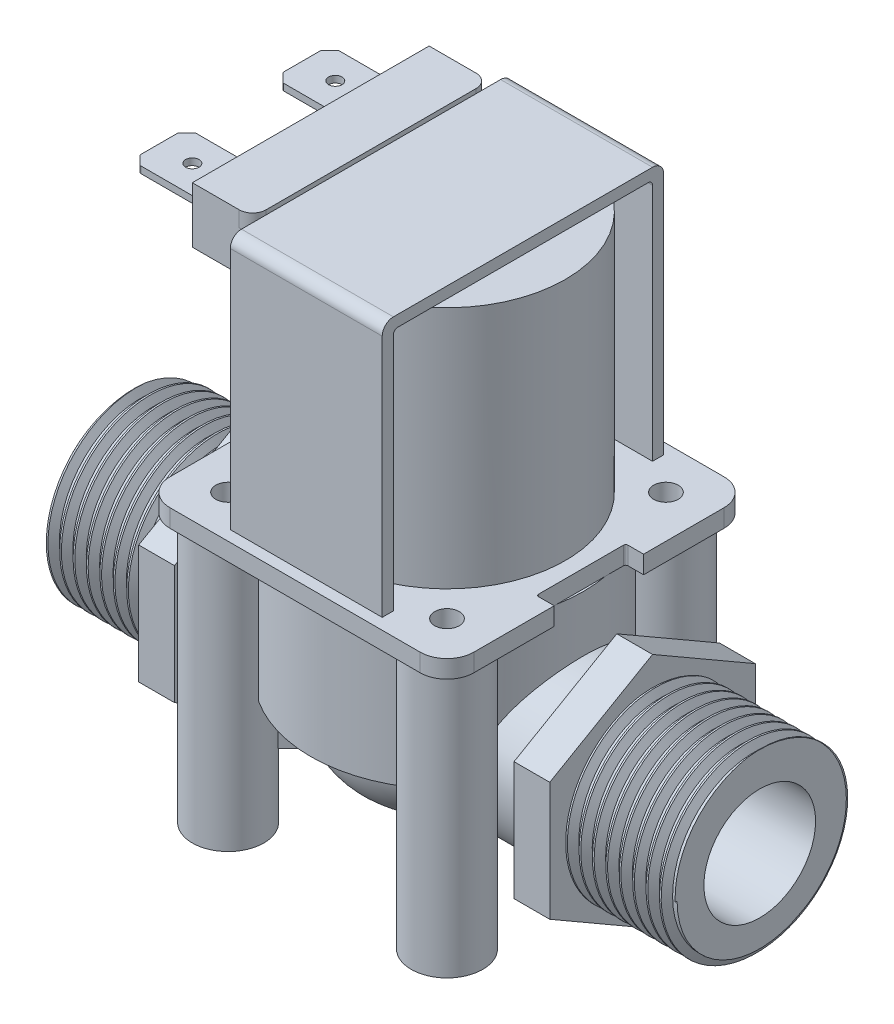
SolidWorks part; units mm, degrees
note: The reader was unsure of these and kept them because the rebuilt part matched: shared geometry of "Sketch14<3>".
ref_plane "Front Plane" through (0, 0, 0) normal (0, 0, 1) x (1, 0, 0)
ref_plane "Top Plane" through (0, 0, 0) normal (0, 1, 0) x (1, 0, 0)
ref_plane "Right Plane" through (0, 0, 0) normal (1, 0, 0) x (0, 0, -1)
sketch "Sketch1" plane through (0, 0, 0) normal (0, 1, 0) x (1, 0, 0)
  line L0 (-17, 17) -> (-13, 17)
  line L1 (-17, -17) -> (17, -17)
  line L2 (-17, -17) -> (-17, 17)
  line L3 (-17, 17) -> (17, 17)
  line L4 (17, -17) -> (17, 17)
  line L5 (-17, -17) -> (17, 17) construction
  line L6 (-17, 17) -> (17, -17) construction
  line L7 (0, 17) -> (0, -17)
  line L8 (17, -17) -> (12.25, -17)
  line L9 (12.25, -17) -> (12.25, -12.25)
  line L10 (-17, 0) -> (17, 0)
  circle A0 centre (12.25, -12.25) radius 1.375
  circle A1 centre (-12.25, -12.25) radius 1.375
  circle A2 centre (12.25, 12.25) radius 1.375
  circle A3 centre (-12.25, 12.25) radius 1.375
  point P0 (0, 0)
  dimension "D2" = 4.75
  dimension "D1" = 34
extrude "Boss-Extrude1" add sketch "Sketch1" along normal blind 2
fillet "Fillet1" radius 3 4 edges at (-17, 1, -17) (17, 1, -17) (17, 1, 17) (-17, 1, 17)
sketch "Sketch2" plane through (0, 2, 0) normal (0, 1, 0) x (1, 0, 0)
  line L0 (0, -17) -> (0, -15.125)
  line L1 (-14, -17) -> (14, -17) construction
  line L2 (-17, 0) -> (17, 0)
  line L3 (-8.5, -15.75) -> (8.5, -15.75)
  line L4 (-8.5, -15.75) -> (-8.5, -14.5)
  line L5 (-8.5, -14.5) -> (8.5, -14.5)
  line L6 (8.5, -15.75) -> (8.5, -14.5)
  line L7 (-8.5, -15.75) -> (8.5, -14.5) construction
  line L8 (-8.5, -14.5) -> (8.5, -15.75) construction
  line L9 (-17, -14) -> (-17, 14) construction
  line L10 (17, -14) -> (17, 14) construction
  line L11 (-8.5, 14.5) -> (8.5, 14.5)
  line L12 (8.5, 15.75) -> (8.5, 14.5)
  line L13 (-8.5, 15.75) -> (8.5, 15.75)
  line L14 (-8.5, 15.75) -> (-8.5, 14.5)
  dimension "D1" = 1.25
  dimension "D2" = 17
extrude "Boss-Extrude2" add sketch "Sketch2" along normal blind 28.5 contours L5 L6 L3 L4 | L11 L12 L13 L14
sketch "Sketch3" plane through (0, 30.5, 0) normal (0, 1, 0) x (1, 0, 0)
  line L1 (-8.5, 14.5) -> (8.5, 14.5)
  line L2 (-8.5, 14.5) -> (-8.5, -14.5)
  line L3 (-8.5, -14.5) -> (8.5, -14.5)
  line L4 (8.5, 14.5) -> (8.5, -14.5)
extrude "Boss-Extrude3" add sketch "Sketch3" against normal blind 1.25
fillet "Fillet2" radius 1.25 2 edges at (0, 30.5, -15.75) (0, 30.5, 15.75)
fillet "Fillet3" radius 0.5 2 edges at (0, 29.25, 14.5) (0, 29.25, -14.5)
sketch "Sketch4" plane through (0, 2, 0) normal (0, 1, 0) x (1, 0, 0)
  circle A0 centre (0, 0) radius 13.25
extrude "Boss-Extrude4" add sketch "Sketch4" along normal up to surface (27.25 mm away) up to face at (0, 29.25, 0)
sketch "Sketch5" plane through (0, 29.25, 0) normal (0, 1, 0) x (1, 0, 0)
  line L1 (0, 13.25) -> (-15.25, 13.25)
  line L2 (0, 13.25) -> (0, -13.25)
  line L3 (0, -13.25) -> (-15.25, -13.25)
  line L4 (-15.25, 13.25) -> (-15.25, -13.25)
  circle A0 centre (0, 0) radius 13.25 construction
  dimension "D1" = 15.25
extrude "Boss-Extrude5" add sketch "Sketch5" against normal blind 4.5 contours L2 L1 L4 L3
sketch "Sketch6" plane through (0, 29.25, 0) normal (0, 1, 0) x (1, 0, 0)
  line L1 (-15.25, 13.25) -> (-10, 13.25)
  line L2 (-15.25, 13.25) -> (-15.25, -13.25)
  line L3 (-15.25, -13.25) -> (-10, -13.25)
  line L4 (-8.5, 11.75) -> (-8.5, -11.75)
  arc A0 (-10, -13.25) -> (-8.5, -11.75) centre (-10, -11.75) ccw
  arc A1 (-8.5, 11.75) -> (-10, 13.25) centre (-10, 11.75) ccw
  point P8 (-8.5, -13.25)
  dimension "D1" = 1.5
extrude "Boss-Extrude6" add sketch "Sketch6" along normal offset from surface (1.75 mm away) 0.5 up to face at (0, 30.5, 0) offset beyond the face yes
sketch "Sketch7" plane through (-15.25, 0, 0) normal (-1, 0, 0) x (0, 0, 1)
  line L0 (13.25, 24.75) -> (13.25, 27.25)
  line L1 (-13.25, 24.75) -> (13.25, 24.75) construction
  line L2 (-13.25, 24.75) -> (13.25, 24.75) construction
  line L3 (13.25, 24.75) -> (13.25, 31) construction
  line L4 (13.25, 27.25) -> (12, 27.25)
  line L5 (12, 26.875) -> (12, 27.625)
  line L6 (0, 31) -> (0, 24.75)
  line L7 (12, 27.625) -> (4, 27.625)
  line L8 (12, 27.625) -> (12, 26.875)
  line L9 (12, 26.875) -> (4, 26.875)
  line L10 (4, 27.625) -> (4, 26.875)
  line L11 (13.25, 31) -> (-13.25, 31) construction
  line L12 (-12, 26.875) -> (-4, 26.875)
  line L13 (-4, 27.625) -> (-4, 26.875)
  line L14 (-12, 27.625) -> (-4, 27.625)
  line L15 (-12, 27.625) -> (-12, 26.875)
  point P12 (12, 27.25)
  dimension "D1" = 8
extrude "Boss-Extrude7" add sketch "Sketch7" along normal blind 9 contours L14 L15 L12 L13 | L7 L10 L9 L5
sketch "Sketch8" plane through (0, 27.625, 0) normal (0, 1, 0) x (1, 0, 0)
  line L0 (-24.25, 11.125) -> (-24.25, 4.875)
  line L1 (-24.25, 12) -> (-24.25, 4) construction
  line L2 (-15.25, 0) -> (-24.25, 0)
  line L7 (-15.25, -13.25) -> (-15.25, 13.25) construction
  line L12 (-16.25, -4) -> (-24.25, -4)
  line L13 (-24.25, 12) -> (-16.25, 12)
  line L14 (-24.25, 12) -> (-24.25, 11.125)
  line L15 (-24.25, 11.125) -> (-16.25, 11.125)
  line L16 (-16.25, 12) -> (-16.25, 11.125)
  line L17 (-16.25, 4.875) -> (-24.25, 4.875)
  line L18 (-16.25, 4.875) -> (-16.25, 4)
  line L19 (-16.25, 4) -> (-24.25, 4)
  line L20 (-24.25, 4.875) -> (-24.25, 4)
  line L21 (-24.25, -4.875) -> (-24.25, -4)
  line L22 (-16.25, -4.875) -> (-24.25, -4.875)
  line L23 (-16.25, -4.875) -> (-16.25, -4)
  line L24 (-24.25, -11.125) -> (-16.25, -11.125)
  line L25 (-16.25, -12) -> (-16.25, -11.125)
  line L26 (-24.25, -12) -> (-16.25, -12)
  line L27 (-24.25, -12) -> (-24.25, -11.125)
  point P5 (-24.25, 8)
  dimension "D1" = 8
extrude "Cut-Extrude1" cut sketch "Sketch8" against normal up to surface (0.75 mm away) contours L15 L16 L13 L14 | L20 L19 L18 L17 | L22 L21 L12 L23 | L24 L25 L26 L27 up to face at (-19.75, 26.875, 8)
chamfer "Chamfer1" distance 1 angle 45 4 edges at (-24.25, 27.25, 11.125) (-24.25, 27.25, 4.875) (-24.25, 27.25, -4.875) (-24.25, 27.25, -11.125)
fillet "Fillet4" radius 0.25 8 edges at (-23.25, 27.25, 11.125) (-24.25, 27.25, 10.125) (-24.25, 27.25, 5.875) (-23.25, 27.25, 4.875) (-24.25, 27.25, -10.125) (-23.25, 27.25, -11.125) (-24.25, 27.25, -5.875) (-23.25, 27.25, -4.875)
sketch "Sketch9" plane through (0, 0, 0) normal (0, -1, 0) x (1, 0, 0)
  line L0 (-17, 14) -> (-17, -14) construction
  line L1 (-17, -5) -> (-17, 5)
  line L2 (0, 17) -> (0, -17)
  line L3 (-17, 5) -> (-15, 5)
  line L4 (-17, 5) -> (-17, -5)
  line L5 (-17, -5) -> (-15, -5)
  line L6 (-15, 5) -> (-15, -5)
  line L7 (-14, 17) -> (14, 17) construction
  line L8 (-14, -17) -> (14, -17) construction
  line L9 (17, -5) -> (15, -5)
  line L10 (15, 5) -> (15, -5)
  line L11 (17, 5) -> (15, 5)
  line L12 (17, 5) -> (17, -5)
  point P5 (-17, 0)
  line M11 (-17, 14) -> (-17, -14)
  line M15 (17, -14) -> (17, 14)
  dimension "D1" = 2
extrude "Cut-Extrude2" cut sketch "Sketch9" against normal up to surface (2 mm away) contours L6 L3 L5 M11 | L11 L10 L9 M15 up to face at (0, 2, 13.25)
fillet "Fillet6" radius 0.25 4 edges at (15, 1, 5) (15, 1, -5) (-15, 1, 5) (-15, 1, -5)
sketch "Sketch10" plane through (0, 27.625, 0) normal (0, 1, 0) x (1, 0, 0)
  line L0 (-24.25, 8) -> (-21.25, 8)
  line L1 (-24.25, 10.0214) -> (-24.25, 5.9786) construction
  line L2 (-21.25, 8) -> (-20.5, 8)
  line L3 (-15.25, 0) -> (-24.25, 0)
  line L4 (-15.25, -13.25) -> (-15.25, 13.25) construction
  circle A0 centre (-20.5, 8) radius 0.75
  circle A1 centre (-20.5, -8) radius 0.75
extrude "Cut-Extrude3" cut sketch "Sketch10" against normal up to surface (0.75 mm away) contours A0 | A1 up to face at (-20.3816, 26.875, 8)
sketch "Sketch11" plane through (0, 0, 0) normal (0, -1, 0) x (1, 0, 0)
  line L0 (16.25, 16.25) -> (12.25, 16.25)
  line L1 (-16.25, -16.25) -> (16.25, -16.25)
  line L2 (-16.25, -16.25) -> (-16.25, 16.25)
  line L3 (-16.25, 16.25) -> (16.25, 16.25)
  line L4 (16.25, -16.25) -> (16.25, 16.25)
  line L5 (-16.25, -16.25) -> (16.25, 16.25) construction
  line L6 (-16.25, 16.25) -> (16.25, -16.25) construction
  line L7 (12.25, 16.25) -> (12.25, 12.25)
  line L8 (0, 16.25) -> (0, -16.25)
  line L9 (-16.25, 0) -> (16.25, 0)
  circle A0 centre (12.25, 12.25) radius 4
  circle A1 centre (-12.25, 12.25) radius 4
  circle A2 centre (12.25, -12.25) radius 4
  circle A3 centre (-12.25, -12.25) radius 4
  circle A4 centre (-12.25, 12.25) radius 1.375
  circle A5 centre (12.25, 12.25) radius 1.375
  circle A6 centre (12.25, -12.25) radius 1.375
  circle A7 centre (-12.25, -12.25) radius 1.375
  point P0 (0, 0)
  dimension "D1" = 32.5
  dimension "D2" = 32.5
extrude "Boss-Extrude8" add sketch "Sketch11" along normal blind 30
sketch "Sketch12" plane through (0, 0, 0) normal (0, -1, 0) x (1, 0, 0)
  line L0 (8.25, 12.25) -> (12.25, 8.25)
  line L1 (10.6036, 9.8964) -> (9.8964, 10.6036)
  line L2 (9.8964, 10.6036) -> (10.6036, 9.8964)
  line L3 (9.8964, 10.6036) -> (-0.7071, 0)
  line L4 (10.6036, 9.8964) -> (0, -0.7071)
  line L5 (-0.7071, 0) -> (0, -0.7071)
  line L6 (-15, 0) -> (15, 0)
  line L7 (-15, 4.75) -> (-15, -4.75) construction
  line L8 (15, 4.75) -> (15, -4.75) construction
  line L9 (0, 17) -> (0, -17)
  line L10 (-14, 17) -> (14, 17) construction
  line L11 (-14, -17) -> (14, -17) construction
  line L12 (-10.6036, 9.8964) -> (0, -0.7071)
  line L13 (0.7071, 0) -> (0, -0.7071)
  line L14 (-9.8964, 10.6036) -> (0.7071, 0)
  line L15 (-9.8964, 10.6036) -> (-10.6036, 9.8964)
  line L16 (10.6036, -9.8964) -> (0, 0.7071)
  line L17 (-0.7071, 0) -> (0, 0.7071)
  line L18 (9.8964, -10.6036) -> (-0.7071, 0)
  line L19 (9.8964, -10.6036) -> (10.6036, -9.8964)
  line L20 (-10.6036, -9.8964) -> (0, 0.7071)
  line L21 (-9.8964, -10.6036) -> (-10.6036, -9.8964)
  line L22 (-9.8964, -10.6036) -> (0.7071, 0)
  line L23 (0.7071, 0) -> (0, 0.7071)
  circle A0 centre (12.25, 12.25) radius 4 construction
  circle A1 centre (12.25, 12.25) radius 4 construction
  point P9 (10.25, 10.25)
  circle M11 centre (-12.25, -12.25) radius 4
  circle M12 centre (12.25, -12.25) radius 4
  circle M13 centre (12.25, 12.25) radius 4
  circle M14 centre (-12.25, 12.25) radius 4
extrude "Boss-Extrude9" add sketch "Sketch12" along normal blind 22.5 contours L3 L14 L4 M13 | L22 L5 L20 M11 | L18 L16 L4 M12 | L14 L9 L6 | L9 L3 L6 | L9 L6 L5 | L6 L9 L4 | L14 L12 L3 M14
sketch "Sketch13" plane through (0, 0, 0) normal (0, -1, 0) x (1, 0, 0)
  circle A0 centre (0, 0) radius 11.5
extrude "Boss-Extrude10" add sketch "Sketch13" along normal blind 25
fillet "Fillet7" radius 7.5 1 edges at (0, -25, -11.5)
sketch "Sketch14" plane through (0, 0, 0) normal (0, -1, 0) x (1, 0, 0)
  line L0 (-14.25, -0.5) -> (-14.25, 0.5)
  line L1 (0.5, 14.25) -> (-0.5, 14.25)
  line L2 (-14.25, 0.5) -> (-11.4891, 0.5)
  line L3 (-14.25, 0.5) -> (-14.25, -0.5)
  line L4 (-14.25, -0.5) -> (-11.4891, -0.5)
  line L5 (-11.4891, 0.5) -> (-11.4891, -0.5)
  line L6 (0.5, 14.25) -> (0.5, 11.4891)
  line L7 (0.5, 11.4891) -> (-0.5, 11.4891)
  line L8 (-0.5, 14.25) -> (-0.5, 11.4891)
  line L9 (14.25, -0.5) -> (14.25, 0.5)
  line L10 (14.25, -0.5) -> (11.4891, -0.5)
  line L11 (11.4891, -0.5) -> (11.4891, 0.5)
  line L12 (14.25, 0.5) -> (11.4891, 0.5)
  line L13 (-0.5, -14.25) -> (0.5, -14.25)
  line L14 (-0.5, -14.25) -> (-0.5, -11.4891)
  line L15 (-0.5, -11.4891) -> (0.5, -11.4891)
  line L16 (0.5, -14.25) -> (0.5, -11.4891)
  circle A0 centre (0, 0) radius 15.25
  circle A1 centre (0, 0) radius 14.25
  arc A2 (-8.4776, 7.7705) -> (-8.4776, -7.7705) centre (0, 0) ccw construction
  point P7 (-14.25, 0)
  point P26 (0, 0)
  dimension "D1" = 4
extrude "Boss-Extrude14" add sketch "Sketch14" along normal blind 16 contours A0 | A1
extrude "Boss-Extrude15" add sketch "Sketch14<3>" along normal blind 16 contours L2 A1 L4 L16 | L6 A1 L8 L14 | L10 A1 L12 | A1 L16 A2 L14
sketch "Sketch14<3>" plane through (0, 0, 0) normal (0, -1, 0) x (1, 0, 0) same geometry as "Sketch14"
sketch "Sketch15" plane through (-17, 0, 0) normal (-1, 0, 0) x (0, 0, 1)
  line L0 (0, -25) -> (0, -24.75)
  line L1 (-4, -25) -> (4, -25) construction
  line L2 (0, -24.75) -> (0, -15.5)
  circle A0 centre (0, -15.5) radius 9.25
extrude "Boss-Extrude16" add sketch "Sketch15" along normal blind 18 and the other way offset from surface (52 mm away) 18 other way up to face at (17, 1, 9.5)
sketch "Sketch16" plane through (35, 0, 0) normal (1, 0, 0) x (0, 0, -1)
  circle A0 centre (0, -15.5) radius 6.25
extrude "Cut-Extrude4" cut sketch "Sketch16" against normal up to surface (70 mm away) up to face at (-35, -15.5, 9.25)
thread "Thread1" pitch 1.5 start angle 0, offset 1, length 12.5, pitch 1.5, diameter 18.5
ref_plane "Plane2" through (-36, -15.5, -9.25) normal (0, -1, 0) x (0, 0, -1)
sketch "Thread Profile1" plane through (-36, -15.5, -9.25) normal (0, -1, 0) x (0, 0, -1)
  line L0 (0, 0) -> (0, 1.5) construction
  line L1 (0, 0) -> (0.8119, 0.4687)
  line L2 (0.8119, 0.4687) -> (0.8119, 0.6562)
  line L3 (0.8119, 0.6562) -> (0, 1.125)
  line L4 (0.8119, 0.5625) -> (0, 0.5625) construction
  line L11 (0, 0) -> (0, 1.125)
  point P2 (0, 0)
  dimension "Pitch" = 1.5
  dimension "Profile_Angle" = 60
  dimension "Profile_Land" = 0.1875
  dimension "Profile_Height" = 0.8119
thread "Thread2" pitch 1.5 profile "Thread Profile2" start angle 0, offset 1, length 12.5, pitch 1.5, diameter 18.5
ref_plane "Plane3" through (36, -15.5, 9.25) normal (0, -1, 0) x (0, 0, 1)
sketch "Thread Profile2" plane through (36, -15.5, 9.25) normal (0, -1, 0) x (0, 0, 1)
  line L0 (0, 0) -> (0, 1.5) construction
  line L1 (0, 0) -> (0.8119, 0.4687)
  line L2 (0.8119, 0.4687) -> (0.8119, 0.6562)
  line L3 (0.8119, 0.6562) -> (0, 1.125)
  line L4 (0.8119, 0.5625) -> (0, 0.5625) construction
  line L11 (0, 0) -> (0, 1.125)
  point P2 (0, 0)
  dimension "Pitch" = 1.5
  dimension "Profile_Angle" = 60
  dimension "Profile_Land" = 0.1875
  dimension "Profile_Height" = 0.8119
sketch "Sketch23" plane through (-17, 0, 0) normal (-1, 0, 0) x (0, 0, 1)
  line L0 (-11.5, -15.5) -> (11.5, -15.5)
  line L1 (0, -2.2209) -> (-11.5, -8.8605)
  line L2 (-11.5, -8.8605) -> (-11.5, -22.1395)
  line L3 (-11.5, -22.1395) -> (0, -28.7791)
  line L4 (0, -28.7791) -> (11.5, -22.1395)
  line L5 (11.5, -22.1395) -> (11.5, -8.8605)
  line L6 (11.5, -8.8605) -> (0, -2.2209)
  circle A0 centre (0, -15.5) radius 11.5 construction
extrude "Boss-Extrude18" add sketch "Sketch23" along normal blind 4 from offset 2 contours L4 L5 L0 L2 L3 | L5 L6 L1 L2 L0
sketch "Sketch25" plane through (17, 0, 0) normal (1, 0, 0) x (0, 0, -1)
  line L0 (-11.5, -15.5) -> (11.5, -15.5)
  line L1 (0, -2.2209) -> (-11.5, -8.8605)
  line L2 (-11.5, -8.8605) -> (-11.5, -22.1395)
  line L3 (-11.5, -22.1395) -> (0, -28.7791)
  line L4 (0, -28.7791) -> (11.5, -22.1395)
  line L5 (11.5, -22.1395) -> (11.5, -8.8605)
  line L6 (11.5, -8.8605) -> (0, -2.2209)
  circle A0 centre (0, -15.5) radius 11.5 construction
extrude "Boss-Extrude19" add sketch "Sketch25" along normal blind 4 from offset 2 contours L4 L5 L0 L2 L3 | L5 L6 L1 L2 L0
